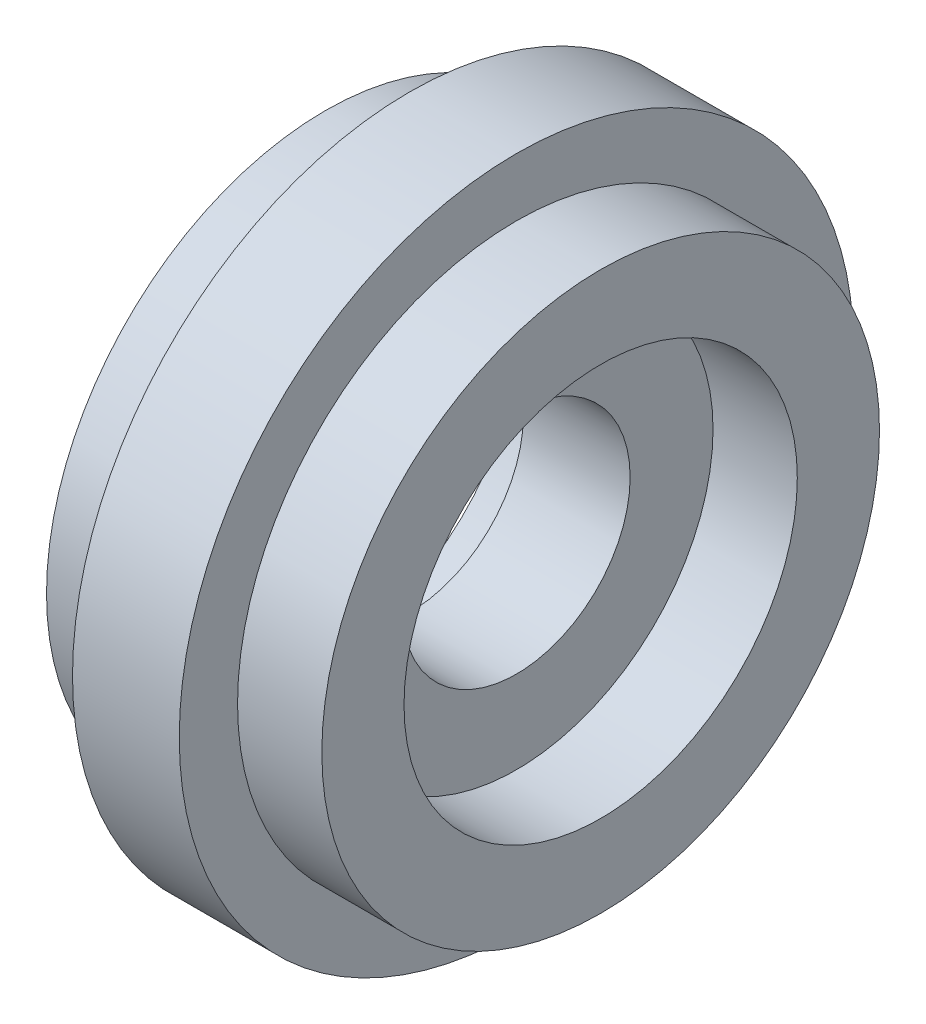
SolidWorks part; units mm, degrees
ref_plane "Ebene vorne" through (0, 0, 0) normal (0, 0, 1) x (1, 0, 0)
ref_plane "Ebene oben" through (0, 0, 0) normal (0, 1, 0) x (1, 0, 0)
ref_plane "Ebene rechts" through (0, 0, 0) normal (1, 0, 0) x (0, 0, -1)
sketch "Skizze1" plane through (0, 0, 0) normal (0, 0, 1) x (1, 0, 0)
  line L0 (0, 0) -> (-15579.6152, 0) construction
  line L1 (0, 0) -> (0, 12)
  line L2 (0, 12) -> (1.9, 12)
  line L3 (1.9, 12) -> (1.9, 9.925)
  line L4 (1.9, 9.925) -> (4.9, 9.925)
  line L5 (4.9, 9.925) -> (4.9, 7)
  line L6 (4.9, 7) -> (1.9, 7)
  line L7 (1.9, 7) -> (1.9, 0)
  line L8 (1.9, 0) -> (0, 0)
  dimension "D1" = 1.9
  dimension "D2" = 4.9
  dimension "D3" = 24
  dimension "D4" = 19.85
  dimension "D5" = 14
revolve "Rotation1" add sketch "Skizze1" angle 360 about L0
hole_wizard "Ø8.1 (8.1) Durchmesser Bohrung1" positions "Skizze2" profile "Skizze3" hole size "Ø8.1" standard "ISO" end condition through all
sketch "Skizze2" plane through (0, 0, 0) normal (-1, 0, 0) x (0, 0, 1)
  point P0 (0, 0)
sketch "Skizze3" plane through (0, 0, 0) normal (0, 1, 0) x (0, 0, 1)
  line L0 (0, 0) -> (0, 4.9)
  line L1 (0, 4.9) -> (4.05, 4.9)
  line L2 (4.05, 4.9) -> (4.05, 0)
  line L5 (4.05, 0) -> (0, 0)
  line L11 (0, -6.35) -> (0, 107.95) construction
  dimension "Bohrerdurchmesser" = 8.1
  dimension "Bohrungstiefe" = 4.9
mirror "Spiegeln1" about plane through (0, 0, 0) normal (1, 0, 0) of "Ø8.1 (8.1) Durchmesser Bohrung1", "Rotation1"
